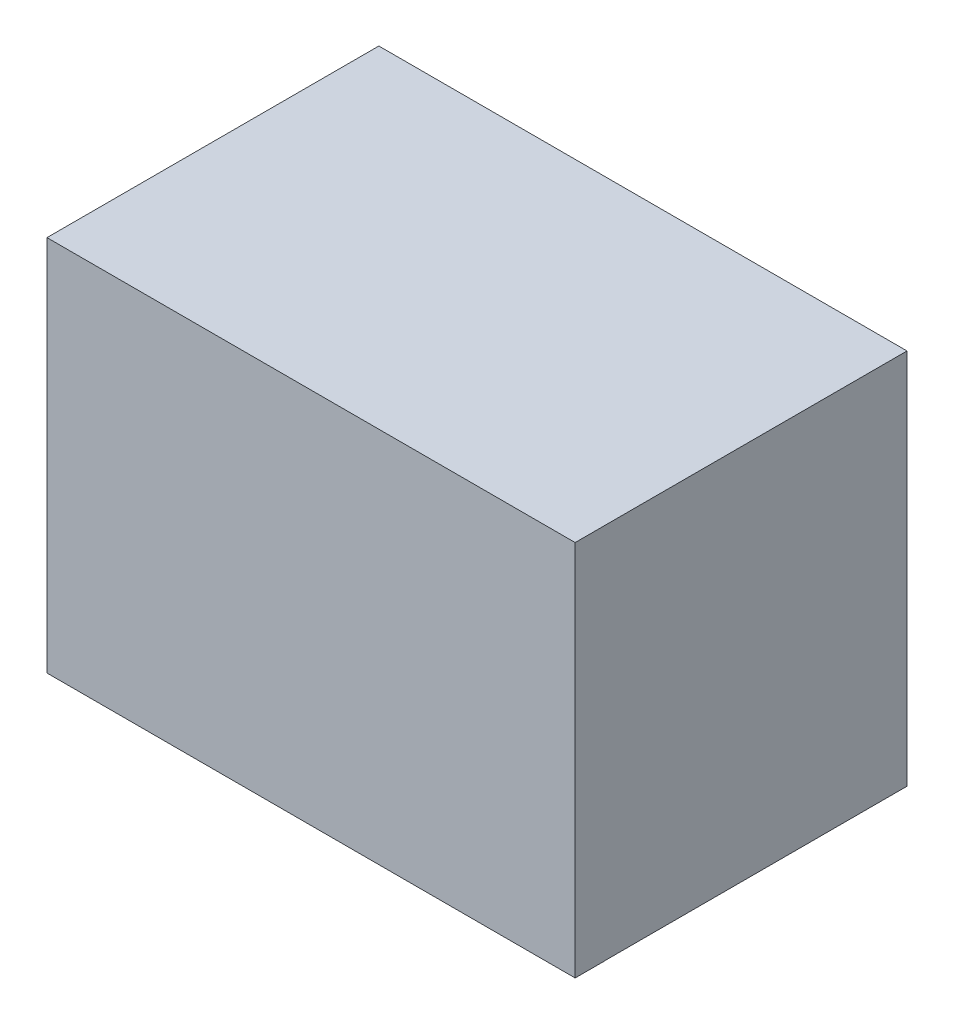
SolidWorks part; units mm, degrees
ref_plane "Front Plane" through (0, 0, 0) normal (0, 0, 1) x (1, 0, 0)
ref_plane "Top Plane" through (0, 0, 0) normal (0, 1, 0) x (1, 0, 0)
ref_plane "Right Plane" through (0, 0, 0) normal (1, 0, 0) x (0, 0, -1)
sketch "Sketch1" plane through (0, 0, 0) normal (0, 0, 1) x (1, 0, 0)
  line L1 (88.9355, -63.4759) -> (-88.9355, -63.4759)
  line L2 (88.9355, -63.4759) -> (88.9355, 63.4759)
  line L3 (88.9355, 63.4759) -> (-88.9355, 63.4759)
  line L4 (-88.9355, -63.4759) -> (-88.9355, 63.4759)
  line L5 (88.9355, -63.4759) -> (-88.9355, 63.4759) construction
  line L6 (88.9355, 63.4759) -> (-88.9355, -63.4759) construction
  point P0 (0, 0)
  dimension "D1" = 177.871
extrude "Boss-Extrude1" add sketch "Sketch1" along normal blind 50.8 and the other way blind 50.8
sketch "Sketch3" plane through (0, 0, 50.8) normal (0, 0, 1) x (1, 0, 0)
  line L1 (-76.2542, -50.7409) -> (76.2542, -50.7409)
  line L2 (-76.2542, -50.7409) -> (-76.2542, 50.7409)
  line L3 (-76.2542, 50.7409) -> (76.2542, 50.7409)
  line L4 (76.2542, -50.7409) -> (76.2542, 50.7409)
  line L5 (-76.2542, -50.7409) -> (76.2542, 50.7409) construction
  line L6 (-76.2542, 50.7409) -> (76.2542, -50.7409) construction
  point P0 (0, 0)
extrude "Cut-Extrude1" cut sketch "Sketch3" against normal blind 88.9
fillet "Fillet1" radius 12.7 8 edges at (-76.2542, -50.7409, 6.35) (-76.2542, 0, -38.1) (0, 50.7409, -38.1) (76.2542, 0, -38.1) (0, -50.7409, -38.1) (76.2542, -50.7409, 6.35) (76.2542, 50.7409, 6.35) (-76.2542, 50.7409, 6.35)
sketch "Sketch4" plane through (0, 0, -38.1) normal (0, 0, 1) x (1, 0, 0)
  line L0 (0, -55.88) -> (0, 55.88) construction
  circle A0 centre (-25.4, 0) radius 1.5875
  dimension "D1" = 3.175
  dimension "D2" = 25.4
extrude "Cut-Extrude2" cut sketch "Sketch4" against normal blind 127 and the other way blind 138.938
sketch "Sketch5" plane through (0, 0, -38.1) normal (0, 0, 1) x (1, 0, 0)
  circle A0 centre (-7.62, 0) radius 3.175
  circle A2 centre (-25.4, 0) radius 1.5875 construction
  dimension "D1" = 6.35
  dimension "D2" = 17.78
extrude "Cut-Extrude3" cut sketch "Sketch5" against normal blind 36.576 and the other way through all contours A0
sketch "Sketch6" plane through (0, 63.4759, 0) normal (0, 1, 0) x (1, 0, 0)
  line L1 (88.9355, -60.9633) -> (-88.9355, -60.9633)
  line L2 (88.9355, -60.9633) -> (88.9355, -50.8)
  line L3 (88.9355, -50.8) -> (-88.9355, -50.8)
  line L4 (-88.9355, -60.9633) -> (-88.9355, -50.8)
  line L5 (88.9355, -60.9633) -> (-88.9355, -50.8) construction
  line L6 (88.9355, -50.8) -> (-88.9355, -60.9633) construction
  point P0 (0, -55.8817)
extrude "Boss-Extrude2" add sketch "Sketch6" against normal blind 127
